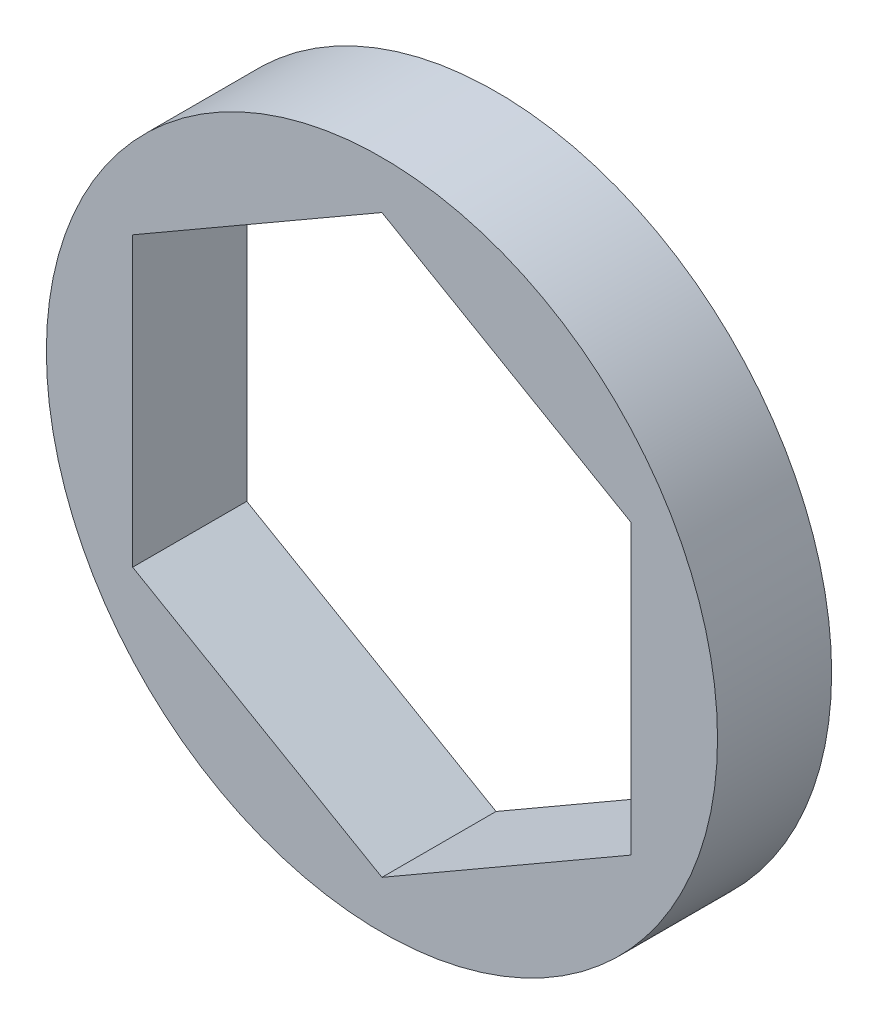
SolidWorks part; units mm, degrees
material "Nylon 101"
ref_plane "Front Plane" through (0, 0, 0) normal (0, 0, 1) x (1, 0, 0)
ref_plane "Top Plane" through (0, 0, 0) normal (0, 1, 0) x (1, 0, 0)
ref_plane "Right Plane" through (0, 0, 0) normal (1, 0, 0) x (0, 0, -1)
sketch "Sketch1" plane through (0, 0, 0) normal (0, 0, 1) x (1, 0, 0)
  line L1 (6.604, 3.8128) -> (0, 7.6256)
  line L2 (0, 7.6256) -> (-6.604, 3.8128)
  line L3 (-6.604, 3.8128) -> (-6.604, -3.8128)
  line L4 (-6.604, -3.8128) -> (0, -7.6256)
  line L5 (0, -7.6256) -> (6.604, -3.8128)
  line L6 (6.604, -3.8128) -> (6.604, 3.8128)
  circle A0 centre (0, 0) radius 6.604 construction
  circle A1 centre (0, 0) radius 8.89
  dimension "D1" = 13.208
  dimension "D2" = 17.78
extrude "Boss-Extrude1" add sketch "Sketch1" along normal blind 3.0226
